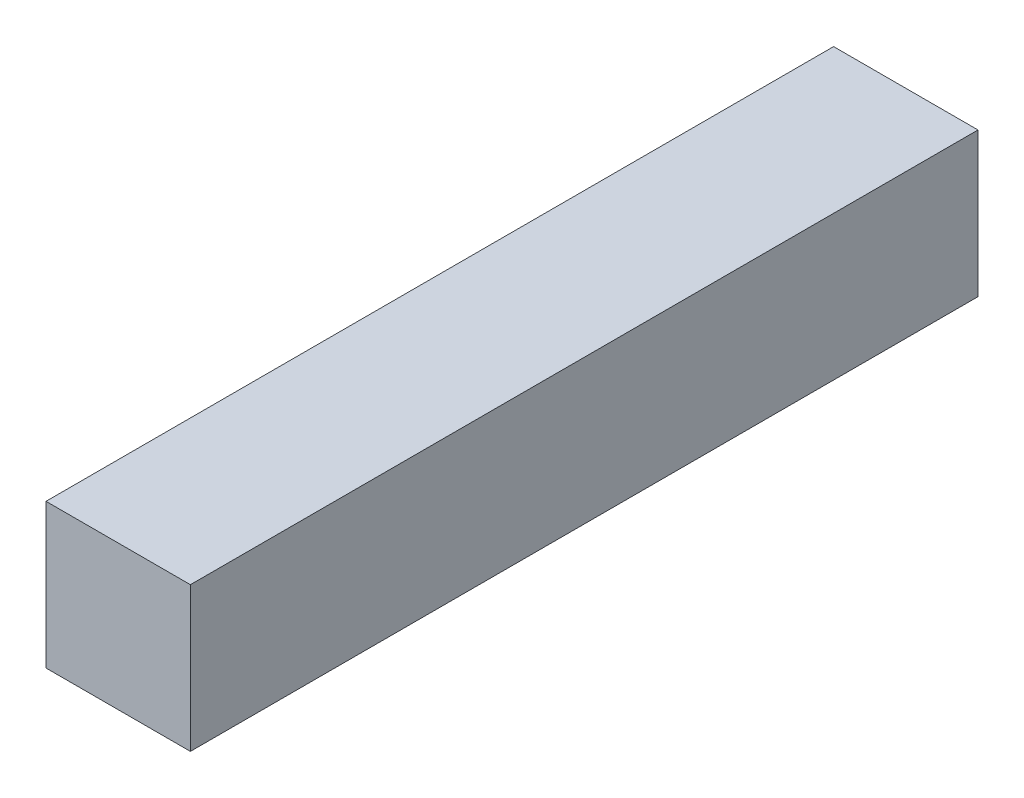
SolidWorks part; units mm, degrees
ref_plane "Front Plane" through (0, 0, 0) normal (0, 0, 1) x (1, 0, 0)
ref_plane "Top Plane" through (0, 0, 0) normal (0, 1, 0) x (1, 0, 0)
ref_plane "Right Plane" through (0, 0, 0) normal (1, 0, 0) x (0, 0, -1)
sketch "Sketch1" plane through (0, 0, 0) normal (0, 0, 1) x (1, 0, 0)
  line L0 (-6.35, -6.35) -> (-6.35, 63.5)
  line L1 (0, 0) -> (57.15, 0)
  line L2 (0, 0) -> (0, 57.15)
  line L3 (0, 57.15) -> (57.15, 57.15)
  line L4 (57.15, 0) -> (57.15, 57.15)
  line L5 (-6.35, 63.5) -> (63.5, 63.5)
  line L6 (63.5, -6.35) -> (63.5, 63.5)
  line L7 (-6.35, -6.35) -> (63.5, -6.35)
  dimension "D1" = 57.15
  dimension "D2" = 6.35
extrude "Boss-Extrude1" add sketch "Sketch1" along normal blind 381 contours L0 L5 L6 L7
extrude "Cut-Extrude1" cut sketch "Sketch1<3>" along normal offset from surface (374.65 mm away) 6.35 contours L3 L4 L1 L2 up to face at (28.575, 28.575, 381)
sketch "Sketch1<3>" plane through (0, 0, 0) normal (0, 0, 1) x (1, 0, 0) same geometry as "Sketch1"
sketch "Sketch2" plane through (0, -6.35, 0) normal (0, -1, 0) x (1, 0, 0)
  line L0 (28.575, 349.25) -> (-6.35, 381) construction
  line L1 (28.575, 349.25) -> (63.5, 381) construction
  circle A0 centre (28.575, 349.25) radius 6.35
  dimension "D1" = 12.7
  dimension "D2" = 31.75
extrude "Cut-Extrude2" cut sketch "Sketch2" against normal up to surface (6.35 mm away) up to face at (28.575, 0, 187.325)
